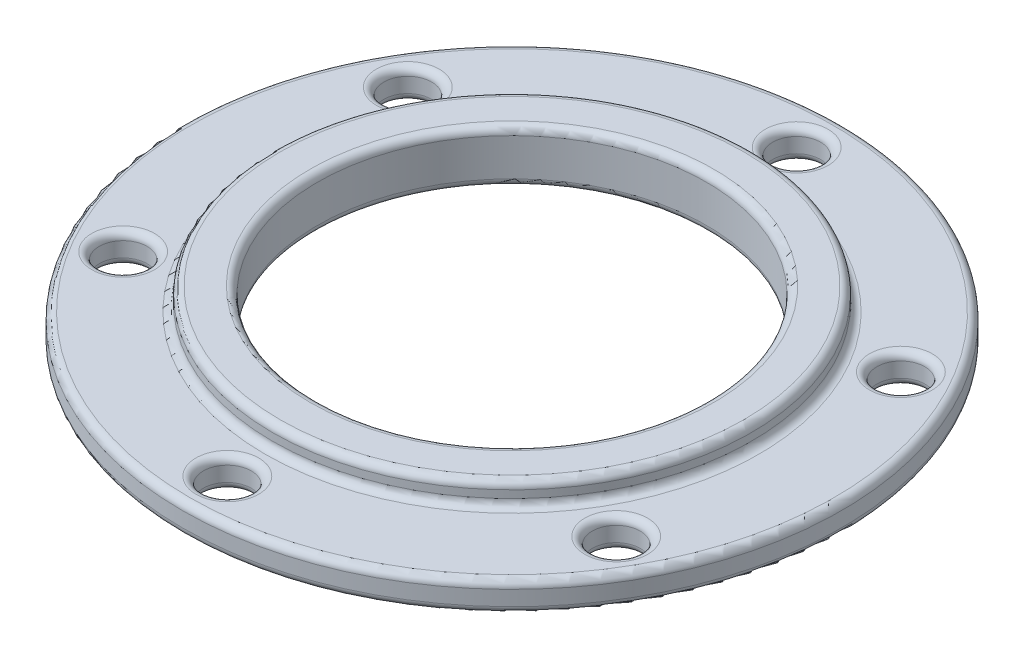
SolidWorks part; units mm, degrees
ref_plane "Front Plane" through (0, 0, 0) normal (0, 0, 1) x (1, 0, 0)
ref_plane "Top Plane" through (0, 0, 0) normal (0, 1, 0) x (1, 0, 0)
ref_plane "Right Plane" through (0, 0, 0) normal (1, 0, 0) x (0, 0, -1)
sketch "Sketch1" plane through (0, 0, 0) normal (0, 1, 0) x (1, 0, 0)
  circle A0 centre (0, 0) radius 22.025
  arc A1 (-0.6528, -22.0153) -> (-0.6528, 22.0153) centre (0, 0) ccw construction
  circle A2 centre (0, 19.025) radius 1.6
  circle A3 centre (16.4761, 9.5125) radius 1.6
  circle A4 centre (16.4761, -9.5125) radius 1.6
  circle A5 centre (0, -19.025) radius 1.6
  circle A6 centre (-16.4761, -9.5125) radius 1.6
  circle A7 centre (-16.4761, 9.5125) radius 1.6
  circle A8 centre (0, 0) radius 13
  point P21 (0, 0)
  dimension "D1" = 3.2
  dimension "D3" = 26
  dimension "D4" = 44.05
  dimension "D2" = 6
extrude "Boss-Extrude1" add sketch "Sketch1" against normal blind 2
ref_axis "Axis1" through (0, -0.25, 0) along (0, 1, 0)
sketch "Sketch2" plane through (0, 0, 0) normal (0, 1, 0) x (1, 0, 0)
  circle A0 centre (0, 0) radius 13
  circle A1 centre (0, 0) radius 16
  dimension "D1" = 26
  dimension "D2" = 32
extrude "Boss-Extrude2" add sketch "Sketch2" along normal blind 1.5
fillet "Fillet1" radius 0.5 18 edges at (0, 0, 22.025) (0, 0, -17.425) (16.4761, 0, -7.9125) (16.4761, 0, 11.1125) (0, 0, 20.625) (-16.4761, 0, 11.1125) (-16.4761, 0, -7.9125) (0, -2, 22.025) (0, -2, -17.425) (0, -2, 13) (16.4761, -2, -7.9125) (16.4761, -2, 11.1125) (0, -2, 20.625) (-16.4761, -2, 11.1125) (-16.4761, -2, -7.9125) (0, 0, 16) (0, 1.5, 13) (0, 1.5, 16)
